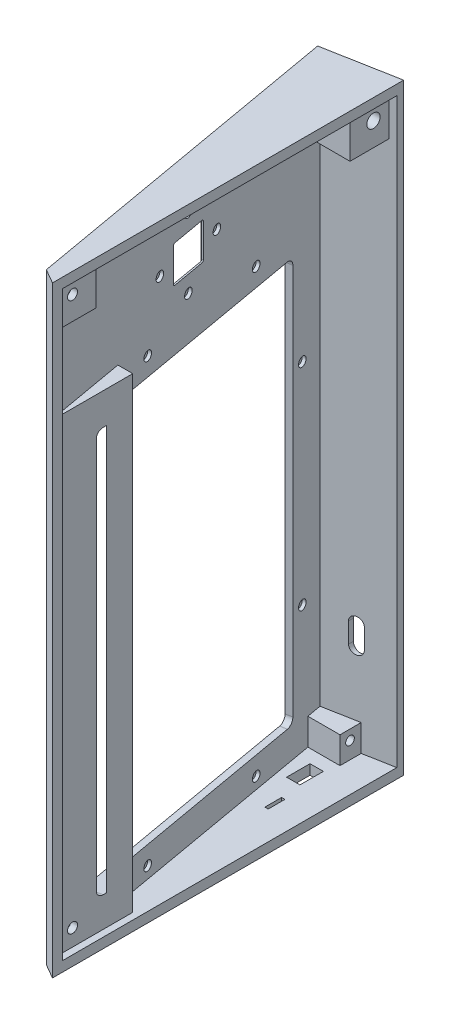
SolidWorks part; units mm, degrees
ref_plane "前视基准面" through (0, 0, 0) normal (0, 0, 1) x (1, 0, 0)
ref_plane "上视基准面" through (0, 0, 0) normal (0, 1, 0) x (1, 0, 0)
ref_plane "右视基准面" through (0, 0, 0) normal (1, 0, 0) x (0, 0, -1)
other "Configuration Table"
sketch "草图1" plane through (0, 0, 0) normal (0, 1, 0) x (1, 0, 0)
  line L0 (82.9035, -37.3993) -> (82.9035, -142.3993)
  line L1 (82.9035, -142.3993) -> (78.5734, -139.8993)
  line L2 (78.5734, -139.8993) -> (61.2086, -41.4185)
  line L3 (61.2086, -41.4185) -> (82.9035, -37.3993)
  dimension "D1" = 100
  dimension "D2" = 105
  dimension "D3" = 5
  dimension "D4" = 170
  dimension "D5" = 60
  dimension "D6" = 90.496
  dimension "D7" = 79.504
extrude "凸台-拉伸1" add sketch "草图1" along normal blind 180
sketch "草图5" plane through (52.2799, 0, -9.2184) normal (-0.9848, 0, 0.1736) x (0.1736, 0, 0.9848)
  line L0 (51.418, 180) -> (51.418, 0) construction
  line L1 (139.418, 12) -> (63.418, 12)
  line L2 (139.418, 12) -> (139.418, 133)
  line L3 (139.418, 133) -> (63.418, 133)
  line L4 (63.418, 12) -> (63.418, 133)
  line L5 (151.418, 180) -> (151.418, 0) construction
  line L6 (51.418, 0) -> (151.418, 0) construction
  dimension "D1" = 76
  dimension "D2" = 121
  dimension "D3" = 12
  dimension "D4" = 12
  dimension "D5" = 12
extrude "切除-拉伸2" cut sketch "草图5" against normal blind 2
sketch "草图7" plane through (82.9035, 0, 0) normal (1, 0, 0) x (0, 0, -1)
  line L8 (-139.3993, 3) -> (-40.3993, 3)
  line L9 (-40.3993, 3) -> (-40.3993, 177)
  line L10 (-40.3993, 177) -> (-139.3993, 177)
  line L11 (-139.3993, 177) -> (-139.3993, 3)
  line L12 (-139.3993, 3) -> (-40.3993, 3)
  line L13 (-40.3993, 3) -> (-40.3993, 177)
  line L14 (-40.3993, 177) -> (-139.3993, 177)
  line L15 (-139.3993, 177) -> (-139.3993, 3)
  dimension "D1" = 3
extrude "切除-拉伸3" cut sketch "草图7" against normal up to surface (19.8438 mm away) up to face at (71.8606, 72.5, 90.3116)
sketch "草图10" plane through (54.2496, 0, -9.5657) normal (0.9848, 0, -0.1736) x (-0.1736, 0, -0.9848)
  line L1 (-63.418, 12) -> (-59.918, 12) construction
  line L2 (-63.418, 12) -> (-63.418, 41) construction
  line L3 (-63.418, 41) -> (-59.918, 41) construction
  line L4 (-59.918, 12) -> (-59.918, 41) construction
  line L5 (-63.418, 133) -> (-59.918, 133) construction
  line L6 (-63.418, 133) -> (-63.418, 104) construction
  line L7 (-63.418, 104) -> (-59.918, 104) construction
  line L8 (-59.918, 133) -> (-59.918, 104) construction
  circle A0 centre (-59.918, 104) radius 1.4
  circle A1 centre (-59.918, 41) radius 1.4
  dimension "D1" = 29
  dimension "D2" = 29
  dimension "D3" = 3.5
  dimension "D4" = 3.5
extrude "切除-拉伸5" cut sketch "草图10" against normal blind 1
sketch "草图11" plane through (54.2496, 0, -9.5657) normal (0.9848, 0, -0.1736) x (-0.1736, 0, -0.9848)
  line L0 (-76.918, 6.5) -> (-116.918, 6.5) construction
  line L1 (-63.418, 133) -> (-76.918, 133) construction
  line L2 (-63.418, 133) -> (-63.418, 138.5) construction
  line L3 (-63.418, 138.5) -> (-76.918, 138.5) construction
  line L4 (-76.918, 133) -> (-76.918, 138.5) construction
  line L5 (-63.418, 12) -> (-76.918, 12) construction
  line L6 (-63.418, 12) -> (-63.418, 6.5) construction
  line L7 (-63.418, 6.5) -> (-76.918, 6.5) construction
  line L8 (-76.918, 12) -> (-76.918, 6.5) construction
  line L9 (-76.918, 138.5) -> (-116.918, 138.5) construction
  circle A0 centre (-116.918, 138.5) radius 1.4
  circle A1 centre (-76.918, 138.5) radius 1.4
  circle A2 centre (-116.918, 6.5) radius 1.4
  circle A3 centre (-76.918, 6.5) radius 1.4
  dimension "D1" = 13.5
  dimension "D2" = 5.5
  dimension "D3" = 13.5
  dimension "D4" = 5.5
  dimension "D5" = 40
  dimension "D6" = 40
extrude "切除-拉伸6" cut sketch "草图11" against normal blind 1
sketch "草图12" plane through (82.9035, 0, 0) normal (1, 0, 0) x (0, 0, -1)
  line L1 (-139.3993, 3) -> (-116.3993, 3)
  line L2 (-139.3993, 3) -> (-139.3993, 142.5)
  line L3 (-139.3993, 142.5) -> (-116.3993, 142.5)
  line L4 (-116.3993, 3) -> (-116.3993, 142.5)
  line L6 (-127.7343, 133) -> (-52.8889, 133) construction
  dimension "D1" = 9.5
  dimension "D2" = 23
extrude "凸台-拉伸3" add sketch "草图12" against normal up to surface (2.3874 mm away) up to face at (67.3631, 138.5, 64.8051)
sketch "草图13" plane through (54.2496, 0, -9.5657) normal (-0.9848, 0, 0.1736) x (0.1736, 0, 0.9848)
  line L4 (127.9081, 12) -> (139.418, 12)
  line L5 (139.418, 12) -> (139.418, 133)
  line L6 (139.418, 133) -> (127.9081, 133)
  line L7 (127.9081, 133) -> (127.9081, 12)
  line L8 (127.9081, 12) -> (139.418, 12)
  line L9 (139.418, 12) -> (139.418, 133)
  line L10 (139.418, 133) -> (127.9081, 133)
  line L11 (127.9081, 133) -> (127.9081, 12)
  dimension "D1" = 0
extrude "切除-拉伸7" cut sketch "草图13" against normal blind 2
sketch "草图14" plane through (52.2799, 0, -9.2184) normal (-0.9848, 0, 0.1736) x (0.1736, 0, 0.9848)
  line L0 (51.418, 180) -> (51.418, 0) construction
  line L1 (96.418, 151) -> (107.418, 151)
  line L2 (96.418, 151) -> (96.418, 162)
  line L3 (96.418, 162) -> (107.418, 162)
  line L4 (107.418, 151) -> (107.418, 162)
  line L5 (139.418, 133) -> (63.418, 133) construction
  line L6 (51.418, 180) -> (151.418, 180) construction
  dimension "D1" = 11
  dimension "D2" = 11
  dimension "D3" = 45
  dimension "D4" = 18
  dimension "D5" = 18
extrude "切除-拉伸8" cut sketch "草图14" against normal blind 2
sketch "草图17" plane through (9.4497, 0, 51.0074) normal (-0.1822, 0, -0.9833) x (-0.9833, 0, 0.1822)
  line L1 (-74.7037, 180) -> (-52.6396, 180)
  line L2 (-74.7037, 180) -> (-74.7037, 0)
  line L3 (-74.7037, 0) -> (-52.6396, 0)
  line L4 (-52.6396, 180) -> (-52.6396, 0)
extrude "凸台-拉伸9" add sketch "草图17" against normal blind 2
sketch "草图18" plane through (0, 0, 0) normal (0, -1, 0) x (1, 0, 0)
  line L0 (82.9035, 39.4333) -> (82.9035, 37.3993)
  line L1 (83.2679, 39.3658) -> (82.9035, 39.4333) construction
  line L2 (83.2679, 39.3658) -> (82.9035, 37.3993) construction
  line L3 (83.2679, 39.3658) -> (82.9035, 37.3993)
  line L4 (83.2679, 39.3658) -> (82.9035, 39.4333)
extrude "切除-拉伸9" cut sketch "草图18" against normal up to surface (180 mm away) up to face at (78.6267, 180, 73.3192)
sketch "草图19" plane through (0, 3, 0) normal (0, 1, 0) x (1, 0, 0)
  line L0 (82.9035, -40.3993) -> (82.9035, -36.7908) construction
  line L1 (77.596, -40.4166) -> (82.9035, -39.4333)
  line L2 (63.5225, -43.0238) -> (77.6894, -40.3993) construction
  line L3 (82.9035, -39.4333) -> (82.9035, -40.3993)
  line L4 (82.9035, -40.3993) -> (77.596, -40.4166)
extrude "切除-拉伸10" cut sketch "草图19" along normal up to surface (174 mm away) up to face at (77.507, 177, 80.5242)
sketch "草图20" plane through (82.9035, 0, 0) normal (1, 0, 0) x (0, 0, -1)
  line L1 (-139.3993, 142.5) -> (-116.3993, 142.5)
  line L2 (-139.3993, 142.5) -> (-139.3993, 3)
  line L3 (-139.3993, 3) -> (-116.3993, 3)
  line L4 (-116.3993, 142.5) -> (-116.3993, 3)
extrude "切除-拉伸11" cut sketch "草图20" against normal blind 2
sketch "草图21" plane through (54.2496, 0, -9.5657) normal (0.9848, 0, -0.1736) x (-0.1736, 0, -0.9848)
  line L0 (-107.418, 156.5) -> (-112.418, 156.5) construction
  line L1 (-107.418, 151) -> (-107.418, 162) construction
  line L2 (-101.918, 162) -> (-101.918, 167) construction
  line L3 (-107.418, 162) -> (-96.418, 162) construction
  line L4 (-96.418, 156.5) -> (-91.418, 156.5) construction
  line L5 (-96.418, 162) -> (-96.418, 151) construction
  line L6 (-101.918, 151) -> (-101.918, 146) construction
  line L7 (-96.418, 151) -> (-107.418, 151) construction
  circle A0 centre (-112.418, 156.5) radius 1.4
  circle A1 centre (-91.418, 156.5) radius 1.4
  circle A2 centre (-101.918, 146) radius 1.4
  circle A3 centre (-101.918, 167) radius 1.4
  dimension "D1" = 5
extrude "切除-拉伸12" cut sketch "草图21" against normal blind 1
sketch "草图23" plane through (80.9035, 0, 0) normal (1, 0, 0) x (0, 0, -1)
  line L0 (-51.4333, 8) -> (-51.4333, 26.4031) construction
  line L1 (-139.3993, 3) -> (-127.3993, 3)
  line L2 (-139.3993, 3) -> (-139.3993, 15)
  line L3 (-139.3993, 15) -> (-127.3993, 15)
  line L4 (-127.3993, 3) -> (-127.3993, 15)
  line L5 (-39.4333, 177) -> (-139.3993, 177) construction
  line L11 (-51.4333, 165) -> (-39.4333, 165)
  line L12 (-51.4333, 165) -> (-51.4333, 177)
  line L13 (-51.4333, 177) -> (-39.4333, 177)
  line L14 (-39.4333, 165) -> (-39.4333, 177)
  line L15 (-127.3993, 8) -> (-127.3993, 23.4787) construction
  line L17 (-127.3993, 165) -> (-139.3993, 165)
  line L18 (-127.3993, 165) -> (-127.3993, 177)
  line L19 (-127.3993, 177) -> (-139.3993, 177)
  line L20 (-139.3993, 165) -> (-139.3993, 177)
  dimension "D1" = 12
  dimension "D2" = 12
  dimension "D5" = 0
  dimension "D6" = 12
  dimension "D7" = 12
  dimension "D8" = 12
  dimension "D9" = 12
  dimension "D11" = 0
extrude "凸台-拉伸10" add sketch "草图23" against normal up to surface (0.3874 mm away) up to face at (73.5276, 156.5, 99.7657)
fillet "圆角4" radius 2 5 edges at (64.2772, 133, 53.0625) (78.4592, 133, 127.7343) (64.2772, 12, 53.0625) (77.4744, 12, 127.9079) (80.394, 12, 127.3931)
sketch "草图26" plane through (0, 177, 0) normal (0, 1, 0) x (1, 0, 0)
  line L3 (63.1752, -41.0542) -> (71.9242, -39.4333)
  line L4 (71.9242, -39.4333) -> (62.8894, -39.4333)
  line L5 (62.8894, -39.4333) -> (63.1752, -41.0542)
  line L6 (63.1752, -41.0542) -> (71.9242, -39.4333)
  line L7 (71.9242, -39.4333) -> (62.8894, -39.4333)
  line L8 (62.8894, -39.4333) -> (63.1752, -41.0542)
  dimension "D1" = 0
extrude "切除-拉伸15" cut sketch "草图26" against normal up to next
sketch "草图27" plane through (82.9035, 0, 0) normal (1, 0, 0) x (0, 0, -1)
  line L1 (-39.4333, 3) -> (-47.4333, 3)
  line L2 (-39.4333, 3) -> (-39.4333, 11)
  line L3 (-39.4333, 11) -> (-47.4333, 11)
  line L4 (-47.4333, 3) -> (-47.4333, 11)
  dimension "D1" = 8
  dimension "D2" = 8
extrude "凸台-拉伸11" add sketch "草图27" against normal up to surface (18.6035 mm away) up to face at (73.5276, 156.5, 99.7657)
sketch "草图28" plane through (82.9035, 0, 0) normal (1, 0, 0) x (0, 0, -1)
  line L1 (-47.4333, 3) -> (-39.4333, 3)
  line L2 (-47.4333, 3) -> (-47.4333, 11)
  line L3 (-47.4333, 11) -> (-39.4333, 11)
  line L4 (-39.4333, 3) -> (-39.4333, 11)
extrude "切除-拉伸16" cut sketch "草图28" against normal blind 9
sketch "草图29" plane through (0, 11, 0) normal (0, -1, 0) x (1, 0, 0)
  line L3 (73.9035, 41.1006) -> (73.9035, 39.4333)
  line L4 (73.9035, 39.4333) -> (82.9035, 39.4333)
  line L5 (82.9035, 39.4333) -> (73.9035, 41.1006)
  line L6 (73.9035, 41.1006) -> (73.9035, 39.4333)
  line L7 (73.9035, 39.4333) -> (82.9035, 39.4333)
  line L11 (82.9035, 39.4333) -> (73.9035, 41.1006)
  dimension "D1" = 0
extrude "凸台-拉伸12" add sketch "草图29" along normal up to surface (8 mm away) up to face at (77.0227, 3, 85.6663)
sketch "草图30" plane through (0, 3, 0) normal (0, -1, 0) x (1, 0, 0)
  line L3 (71.9242, 39.4333) -> (63.1752, 41.0542)
  line L4 (63.1752, 41.0542) -> (62.8894, 39.4333)
  line L5 (62.8894, 39.4333) -> (71.9242, 39.4333)
  line L6 (71.9242, 39.4333) -> (63.1752, 41.0542)
  line L7 (63.1752, 41.0542) -> (62.8894, 39.4333)
  line L8 (62.8894, 39.4333) -> (71.9242, 39.4333)
  dimension "D1" = 0
extrude "切除-拉伸17" cut sketch "草图30" against normal up to next
sketch "草图31" plane through (0, 0, 0) normal (0, -1, 0) x (1, 0, 0)
  line L1 (82.9035, 37.3993) -> (68.9035, 37.3993) construction
  line L2 (82.9035, 37.3993) -> (82.9035, 51.3993) construction
  line L3 (82.9035, 51.3993) -> (68.9035, 51.3993) construction
  line L4 (68.9035, 37.3993) -> (68.9035, 51.3993) construction
  line L5 (68.9035, 51.3993) -> (72.9035, 51.3993)
  line L6 (68.9035, 51.3993) -> (68.9035, 58.3993)
  line L7 (68.9035, 58.3993) -> (72.9035, 58.3993)
  line L8 (72.9035, 51.3993) -> (72.9035, 58.3993)
  dimension "D1" = 14
  dimension "D2" = 14
  dimension "D3" = 7
  dimension "D4" = 4
extrude "切除-拉伸18" cut sketch "草图31" against normal up to next
ref_plane "基准面1" through (0, 0, 37.3993) normal (0, 0, -1) x (-1, 0, 0)
ref_plane "基准面2" through (0, 0, 39.7193) normal (0, 0, -1) x (-1, 0, 0)
sketch "草图32" plane through (0, 0, 39.7193) normal (0, 0, -1) x (-1, 0, 0)
  line L0 (-72.7086, 36) -> (-72.7086, 30) construction
  line L1 (-70.7086, 36) -> (-70.7086, 30)
  line L2 (-74.7086, 36) -> (-74.7086, 30)
  line L3 (-82.9035, 180) -> (-61.2086, 180) construction
  line L4 (-61.2086, 180) -> (-61.2086, 0) construction
  arc A0 (-70.7086, 36) -> (-74.7086, 36) centre (-72.7086, 36) ccw
  arc A1 (-74.7086, 30) -> (-70.7086, 30) centre (-72.7086, 30) ccw
  point P2 (-72.7086, 33)
  point P9 (-72.7086, 28)
  point P10 (-72.7086, 38)
  dimension "D1" = 147
  dimension "D2" = 10
  dimension "D3" = 4
  dimension "D4" = 9.5
extrude "切除-拉伸23" cut sketch "草图32" against normal up to surface (1.9733 mm away) up to face at (75.3083, 89, 40.8404)
ref_plane "基准面4" through (0, 0, 40.2193) normal (0, 0, -1) x (-1, 0, 0)
sketch "草图35" plane through (0, 0, 40.2193) normal (0, 0, -1) x (-1, 0, 0)
  line L0 (-74.7086, 36) -> (-74.7086, 30) construction
  line L1 (-76.7086, 41) -> (-68.7086, 41)
  line L2 (-76.7086, 41) -> (-76.7086, 25)
  line L3 (-76.7086, 25) -> (-68.7086, 25)
  line L4 (-68.7086, 41) -> (-68.7086, 25)
  line L5 (-70.7086, 30) -> (-70.7086, 36) construction
  arc A0 (-70.7086, 36) -> (-74.7086, 36) centre (-72.7086, 36) ccw construction
  arc A1 (-74.7086, 30) -> (-70.7086, 30) centre (-72.7086, 30) ccw construction
  dimension "D1" = 5
  dimension "D2" = 5
  dimension "D3" = 2
  dimension "D4" = 2
extrude "切除-拉伸25" cut sketch "草图35" along normal up to surface (0.1902 mm away) up to face at (72.0561, 90, 39.4089)
fillet "圆角5" radius 0.5 4 edges at (76.7086, 25, 39.3831) (76.7086, 41, 39.3831) (68.7086, 25, 40.1241) (68.7086, 41, 40.1241)
sketch "草图36" plane through (0, 0, 0) normal (0, -1, 0) x (1, 0, 0)
  line L1 (82.9035, 37.3993) -> (74.4035, 37.3993) construction
  line L2 (82.9035, 37.3993) -> (82.9035, 64.3993) construction
  line L3 (82.9035, 64.3993) -> (74.4035, 64.3993) construction
  line L4 (74.4035, 37.3993) -> (74.4035, 64.3993) construction
  line L5 (74.4035, 64.3993) -> (73.4035, 64.3993)
  line L6 (74.4035, 64.3993) -> (74.4035, 69.3993)
  line L7 (74.4035, 69.3993) -> (73.4035, 69.3993)
  line L8 (73.4035, 64.3993) -> (73.4035, 69.3993)
  dimension "D1" = 8.5
  dimension "D2" = 27
  dimension "D3" = 1
  dimension "D4" = 5
extrude "切除-拉伸26" cut sketch "草图36" against normal up to next
sketch "草图37" plane through (0, 0, 0) normal (0, -1, 0) x (1, 0, 0)
  line L0 (73.4035, 66.8993) -> (74.4035, 66.8993) construction
  line L1 (73.4035, 69.3993) -> (73.4035, 64.3993) construction
  line L2 (74.4035, 64.3993) -> (74.4035, 69.3993) construction
  line L3 (73.9035, 64.3993) -> (73.9035, 69.3993) construction
  line L4 (73.4035, 64.3993) -> (74.4035, 64.3993) construction
  line L5 (74.4035, 69.3993) -> (73.4035, 69.3993) construction
  line L7 (74.9035, 69.8993) -> (72.9035, 69.8993)
  line L8 (74.9035, 69.8993) -> (74.9035, 63.8993)
  line L9 (74.9035, 63.8993) -> (72.9035, 63.8993)
  line L10 (72.9035, 69.8993) -> (72.9035, 63.8993)
  line L11 (74.9035, 69.8993) -> (72.9035, 63.8993) construction
  line L12 (74.9035, 63.8993) -> (72.9035, 69.8993) construction
  point P12 (73.9035, 66.8993)
  dimension "D1" = 6
  dimension "D2" = 2
extrude "切除-拉伸27" cut sketch "草图37" against normal blind 1
sketch "草图38" plane through (73.9035, 0, 0) normal (1, 0, 0) x (0, 0, -1)
  line L0 (-47.4333, 3) -> (-41.1006, 3) construction
  line L1 (-47.4333, 11) -> (-44.4333, 11) construction
  line L2 (-47.4333, 11) -> (-47.4333, 8) construction
  line L3 (-47.4333, 8) -> (-44.4333, 8) construction
  line L4 (-44.4333, 11) -> (-44.4333, 8) construction
  line L5 (-47.4333, 11) -> (-47.4333, 3) construction
  circle A0 centre (-44.4333, 8) radius 1.3
  dimension "D1" = 5
  dimension "D2" = 3
extrude "切除-拉伸28" cut sketch "草图38" against normal blind 3 contours A0
sketch "草图39" plane through (80.9035, 0, 0) normal (1, 0, 0) x (0, 0, -1)
  line L0 (-47.4333, 10.1358) -> (-47.4333, 2.8866) construction
  line L4 (-39.8038, 177) -> (-51.4333, 177) construction
  line L5 (-47.4333, 169) -> (-39.8038, 169) construction
  line L6 (-47.4333, 169) -> (-47.4333, 177) construction
  line L7 (-47.4333, 177) -> (-39.8038, 177) construction
  line L8 (-39.8038, 169) -> (-39.8038, 177) construction
  line L10 (-47.4333, 169) -> (-44.4333, 169) construction
  line L11 (-47.4333, 169) -> (-47.4333, 172) construction
  line L12 (-47.4333, 172) -> (-44.4333, 172) construction
  line L13 (-44.4333, 169) -> (-44.4333, 172) construction
  circle A0 centre (-44.4333, 172) radius 2
  dimension "D1" = 8
  dimension "D2" = 3
  dimension "D3" = 3
extrude "切除-拉伸30" cut sketch "草图39" against normal blind 3
sketch "草图40" plane through (80.9035, 0, 0) normal (1, 0, 0) x (0, 0, -1)
  line L1 (-127.3993, 177) -> (-131.3993, 177) construction
  line L2 (-127.3993, 177) -> (-127.3993, 171) construction
  line L3 (-127.3993, 171) -> (-131.3993, 171) construction
  line L4 (-131.3993, 177) -> (-131.3993, 171) construction
  line L5 (-131.3993, 171) -> (-134.3993, 171) construction
  line L6 (-131.3993, 171) -> (-131.3993, 172) construction
  line L7 (-131.3993, 172) -> (-134.3993, 172) construction
  line L8 (-134.3993, 171) -> (-134.3993, 172) construction
  line L9 (-139.3993, 3) -> (-134.3993, 3) construction
  line L10 (-139.3993, 3) -> (-139.3993, 8) construction
  line L11 (-139.3993, 8) -> (-134.3993, 8) construction
  line L12 (-134.3993, 3) -> (-134.3993, 8) construction
  circle A0 centre (-134.3993, 172) radius 1.5
  circle A1 centre (-134.3993, 8) radius 1.5
  dimension "D5" = 5
  dimension "D1" = 6
  dimension "D2" = 4
  dimension "D3" = 3
  dimension "D4" = 1
  dimension "D6" = 5
extrude "切除-拉伸31" cut sketch "草图40" against normal blind 2
sketch "草图42" plane through (54.2496, 0, -9.5657) normal (-0.9848, 0, 0.1736) x (0.1736, 0, 0.9848)
  line L3 (139.0778, 15) -> (139.0778, 12.8842)
  line L4 (139.418, 14) -> (139.418, 15)
  line L5 (139.418, 15) -> (139.0778, 15)
  line L6 (139.0778, 15) -> (139.0778, 12.8842)
  line L7 (139.418, 14) -> (139.418, 15)
  line L8 (139.418, 15) -> (139.0778, 15)
  arc A1 (139.0778, 12.8842) -> (139.418, 14) centre (137.418, 14) ccw
  arc A2 (139.0778, 12.8842) -> (139.418, 14) centre (137.418, 14) ccw
  dimension "D1" = 0
extrude "切除-拉伸34" cut sketch "草图42" against normal up to surface (2 mm away) up to face at (79.6913, 72.5, 123.2038)
chamfer "倒角1" distance 2 distance2 1.5 4 edges at (69.9778, 151, 91.1513) (69.0228, 156.5, 85.7348) (69.9778, 162, 91.1513) (70.9329, 156.5, 96.5677) first distance on face at (69.9778, 156.5, 91.1513)
fillet "圆角6" radius 0.5 4 edges at (72.6563, 151, 96.2638) (72.6563, 162, 96.2638) (70.7462, 162, 85.431) (70.7462, 151, 85.431)
sketch "草图44" plane through (56.2192, 0, -9.913) normal (-0.9848, 0, 0.1736) x (0.1736, 0, 0.9848)
  line L4 (139.418, 14) -> (139.418, 131)
  line L5 (137.418, 133) -> (128.2608, 133)
  line L6 (128.2608, 133) -> (128.2608, 12)
  line L7 (128.2608, 12) -> (137.418, 12)
  line L8 (139.418, 14) -> (139.418, 131)
  line L9 (137.418, 133) -> (128.2608, 133)
  line L10 (128.2608, 133) -> (128.2608, 12)
  line L11 (128.2608, 12) -> (137.418, 12)
  arc A2 (139.418, 131) -> (137.418, 133) centre (137.418, 131) ccw
  arc A3 (137.418, 12) -> (139.418, 14) centre (137.418, 14) ccw
  arc A4 (139.418, 131) -> (137.418, 133) centre (137.418, 131) ccw
  arc A5 (137.418, 12) -> (139.418, 14) centre (137.418, 14) ccw
  dimension "D1" = 0
extrude "切除-拉伸36" cut sketch "草图44" against normal blind 1
